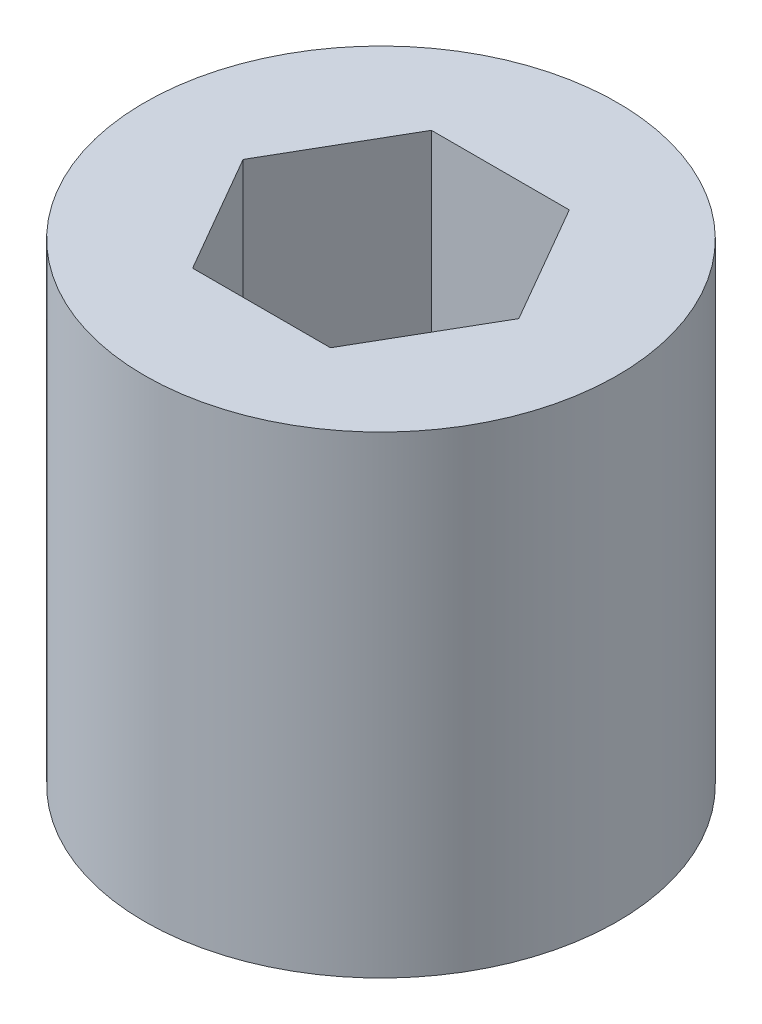
SolidWorks part; units mm, degrees
ref_plane "Front Plane" through (0, 0, 0) normal (0, 0, 1) x (1, 0, 0)
ref_plane "Top Plane" through (0, 0, 0) normal (0, 1, 0) x (1, 0, 0)
ref_plane "Right Plane" through (0, 0, 0) normal (1, 0, 0) x (0, 0, -1)
sketch "Sketch1" plane through (0, 0, 0) normal (0, 1, 0) x (1, 0, 0)
  line L1 (7.4057, 0) -> (3.7028, 6.4135)
  line L2 (3.7028, 6.4135) -> (-3.7028, 6.4135)
  line L3 (-3.7028, 6.4135) -> (-7.4057, 0)
  line L4 (-7.4057, 0) -> (-3.7028, -6.4135)
  line L5 (-3.7028, -6.4135) -> (3.7028, -6.4135)
  line L6 (3.7028, -6.4135) -> (7.4057, 0)
  circle A0 centre (0, 0) radius 12.7
  circle A1 centre (0, 0) radius 6.4135 construction
  point P3 (0, 0)
  point P11 (0, 0)
  dimension "D1" = 12.827
  dimension "D2" = 25.4
extrude "Boss-Extrude1" add sketch "Sketch1" along normal blind 25.4
